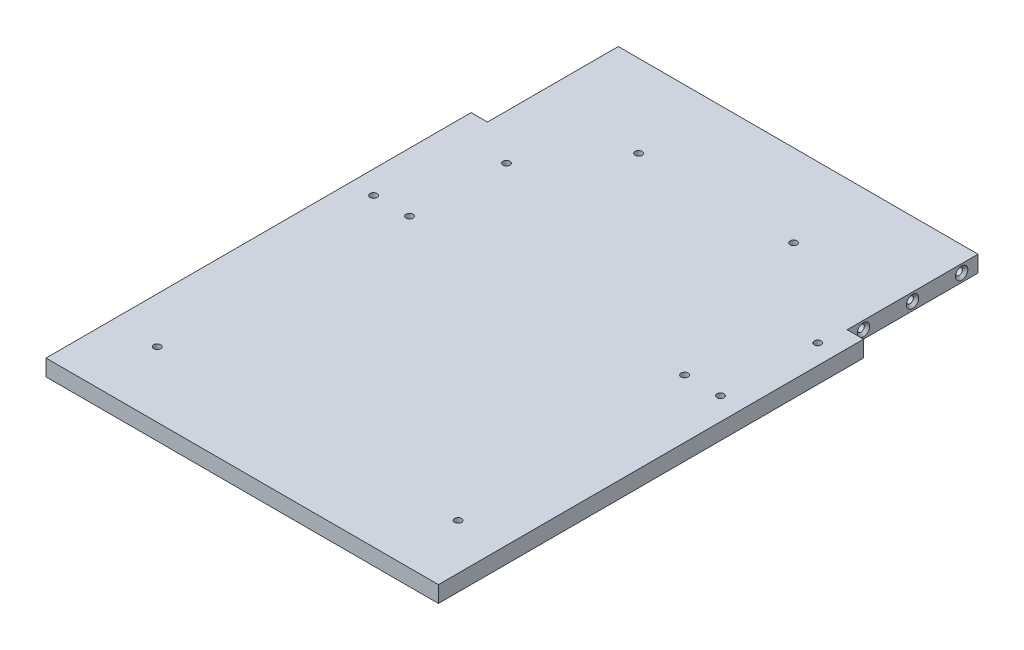
SolidWorks part; units mm, degrees
ref_plane "Front Plane" through (0, 0, 0) normal (0, 0, 1) x (1, 0, 0)
ref_plane "Top Plane" through (0, 0, 0) normal (0, 1, 0) x (1, 0, 0)
ref_plane "Right Plane" through (0, 0, 0) normal (1, 0, 0) x (0, 0, -1)
sketch "Sketch1" plane through (0, 0, 0) normal (0, 1, 0) x (1, 0, 0)
  line L0 (-6.35, 0) -> (-6.35, -50.8)
  line L1 (-6.35, 0) -> (-146.05, 0)
  line L2 (0, -50.8) -> (0, -215.9)
  line L3 (0, -215.9) -> (-152.4, -215.9)
  line L4 (-152.4, -50.8) -> (-152.4, -215.9)
  line L5 (-6.35, -50.8) -> (0, -50.8)
  line L6 (-146.05, 0) -> (-146.05, -50.8)
  line L7 (-146.05, -50.8) -> (-152.4, -50.8)
  point P7 (-3.175, -50.8)
  dimension "D1" = 152.4
  dimension "D2" = 215.9
  dimension "D3" = 50.8
  dimension "D4" = 6.35
  dimension "D5" = 6.35
  dimension "D6" = 50.8
extrude "Boss-Extrude1" add sketch "Sketch1" along normal blind 6.35
sketch "Sketch2" plane through (-6.35, 0, 0) normal (1, 0, 0) x (0, 0, -1)
  line L0 (-50.8, 6.35) -> (-50.8, 0) construction
  line L1 (-50.8, 6.35) -> (-50.8, 0) construction
  line L2 (-50.8, 0) -> (0, 0) construction
  circle A0 centre (-44.45, 3.175) radius 1.8288
  circle A1 centre (-25.4, 3.175) radius 1.8288
  circle A2 centre (-6.35, 3.175) radius 1.8288
  dimension "D4" = 3.175
  dimension "D5" = 3.175
  dimension "D6" = 3.6576
  dimension "D7" = 3.6576
  dimension "D8" = 3.6576
  dimension "D1" = 6.35
  dimension "D2" = 25.4
  dimension "D3" = 44.45
hole_wizard "#6-32 Tapped Hole1" positions "Sketch3" profile "Sketch4" tap size "#6-32" standard "ANSI Inch"
sketch "Sketch3" plane through (-6.35, 0, 0) normal (1, 0, 0) x (0, 0, -1)
  point P0 (-44.45, 3.175)
  point P3 (-25.4, 3.175)
  point P6 (-6.35, 3.175)
sketch "Sketch4" plane through (-6.35, 3.175, 44.45) normal (0, 1, 0) x (0, 0, -1)
  line L0 (0, 0) -> (0, 12.7)
  line L1 (0, 12.7) -> (1.3525, 11.8873)
  line L2 (1.3525, 11.8873) -> (1.3525, 1.0351)
  line L3 (1.3525, 1.0351) -> (2.3876, 0)
  line L5 (2.3876, 0) -> (0, 0)
  line L6 (-1.3525, 1.0351) -> (-2.3876, 0) construction
  line L10 (0, 12.7) -> (-1.3526, 11.8873) construction
  line L11 (0, -6.35) -> (0, 107.95) construction
  dimension "Tap Drill Dia." = 2.7051
  dimension "Tap Drill Depth" = 12.7
  dimension "Near C'Sink Dia." = 4.7752
  dimension "Near C'Sink Angle" = 90
  dimension "Drill Angle" = 118
cosmetic thread "Hole Thread1" parameters "D1"=10.16, "D2"=3.5052
cosmetic thread "Hole Thread2" parameters "D1"=10.16, "D2"=3.5052
cosmetic thread "Hole Thread3" parameters "D1"=10.16, "D2"=3.5052
sketch "Sketch5" plane through (-146.05, 0, 0) normal (-1, 0, 0) x (0, 0, 1)
  circle A0 centre (6.35, 3.175) radius 1.8288
  circle A1 centre (25.4, 3.175) radius 1.8288
  circle A2 centre (44.45, 3.175) radius 1.8288
  dimension "D1" = 3.6576
  dimension "D2" = 3.6576
  dimension "D3" = 3.6576
hole_wizard "#6-32 Tapped Hole2" positions "Sketch6" profile "Sketch7" tap size "#6-32" standard "ANSI Inch"
sketch "Sketch6" plane through (-146.05, 0, 0) normal (-1, 0, 0) x (0, 0, 1)
  point P0 (6.35, 3.175)
  point P3 (25.4, 3.175)
  point P6 (44.45, 3.175)
sketch "Sketch7" plane through (-146.05, 3.175, 6.35) normal (0, 1, 0) x (0, 0, 1)
  line L0 (0, 0) -> (0, 12.7)
  line L1 (0, 12.7) -> (1.3525, 11.8873)
  line L2 (1.3525, 11.8873) -> (1.3525, 1.0351)
  line L3 (1.3525, 1.0351) -> (2.3876, 0)
  line L5 (2.3876, 0) -> (0, 0)
  line L6 (-1.3525, 1.0351) -> (-2.3876, 0) construction
  line L10 (0, 12.7) -> (-1.3526, 11.8873) construction
  line L11 (0, -6.35) -> (0, 107.95) construction
  dimension "Tap Drill Dia." = 2.7051
  dimension "Tap Drill Depth" = 12.7
  dimension "Near C'Sink Dia." = 4.7752
  dimension "Near C'Sink Angle" = 90
  dimension "Drill Angle" = 118
cosmetic thread "Hole Thread4" parameters "D1"=10.16, "D2"=3.5052
cosmetic thread "Hole Thread5" parameters "D1"=10.16, "D2"=3.5052
cosmetic thread "Hole Thread6" parameters "D1"=10.16, "D2"=3.5052
sketch "Sketch9" plane through (0, 6.35, 0) normal (0, 1, 0) x (1, 0, 0)
  line L0 (-152.4, -215.9) -> (0, -215.9) construction
  line L1 (-152.4, -50.8) -> (-152.4, -215.9) construction
  line L2 (0, -215.9) -> (0, -50.8) construction
  circle A0 centre (-134.62, -190.5) radius 1.8288
  circle A1 centre (-17.78, -190.5) radius 1.8288
  dimension "D1" = 17.78
  dimension "D2" = 25.4
  dimension "D3" = 17.78
  dimension "D4" = 3.6576
  dimension "D5" = 3.6576
hole_wizard "#6-32 Tapped Hole3" positions "Sketch12" profile "Sketch13" tap size "#6-32" standard "ANSI Inch" end condition up to next
sketch "Sketch12" plane through (0, 6.35, 0) normal (0, 1, 0) x (1, 0, 0)
  point P0 (-134.62, -190.5)
  point P3 (-17.78, -190.5)
sketch "Sketch13" plane through (-134.62, 6.35, 190.5) normal (1, 0, 0) x (0, 0, 1)
  line L0 (0, 0) -> (0, 6.35)
  line L1 (0, 6.35) -> (1.3525, 6.35)
  line L2 (1.3525, 6.35) -> (1.3525, 0)
  line L5 (1.3525, 0) -> (0, 0)
  line L11 (0, -6.35) -> (0, 107.95) construction
  dimension "Thru Tap Drill Dia." = 2.7051
  dimension "Thru Tap Drill Depth" = 6.35
cosmetic thread "Hole Thread7" parameters "D2"=3.5052
cosmetic thread "Hole Thread8" parameters "D2"=3.5052
sketch "Sketch16" plane through (0, 6.35, 0) normal (0, 1, 0) x (1, 0, 0)
  line L0 (-6.35, -50.8) -> (-6.35, 0) construction
  line L1 (-6.35, 0) -> (-146.05, 0) construction
  circle A0 centre (-45.974, -32.004) radius 1.8288
  circle A1 centre (-106.172, -32.004) radius 1.8288
  dimension "D1" = 39.624
  dimension "D2" = 32.004
  dimension "D3" = 60.198
  dimension "D4" = 32.004
  dimension "D5" = 3.6576
  dimension "D6" = 3.6576
hole_wizard "#6-32 Tapped Hole5" positions "Sketch19" profile "Sketch18" tap size "#6-32" standard "ANSI Inch" end condition up to next
sketch "Sketch19" plane through (0, 6.35, 0) normal (0, 1, 0) x (1, 0, 0)
  point P0 (-106.172, -32.004)
  point P3 (-45.974, -32.004)
sketch "Sketch18" plane through (-106.172, 6.35, 32.004) normal (1, 0, 0) x (0, 0, 1)
  line L0 (0, 0) -> (0, 6.35)
  line L1 (0, 6.35) -> (1.3525, 6.35)
  line L2 (1.3525, 6.35) -> (1.3525, 0)
  line L5 (1.3525, 0) -> (0, 0)
  line L11 (0, -6.35) -> (0, 107.95) construction
  dimension "Thru Tap Drill Dia." = 2.7051
  dimension "Thru Tap Drill Depth" = 6.35
cosmetic thread "Hole Thread11" parameters "D2"=3.5052
cosmetic thread "Hole Thread12" parameters "D2"=3.5052
sketch "Sketch20" plane through (0, 6.35, 0) normal (0, 1, 0) x (1, 0, 0)
  line L0 (0, -50.8) -> (-6.35, -50.8) construction
  line L1 (0, -215.9) -> (0, -50.8) construction
  line L2 (-146.05, -50.8) -> (-152.4, -50.8) construction
  line L4 (-152.4, -50.8) -> (-152.4, -215.9) construction
  circle A0 centre (-128.524, -60.96) radius 1.8987
  circle A1 centre (-129.54, -97.5981) radius 1.8987
  circle A2 centre (-143.4846, -97.6122) radius 1.8987
  circle A3 centre (-7.62, -60.96) radius 1.8987
  circle A4 centre (-22.7076, -97.6122) radius 1.8986
  circle A5 centre (-8.763, -97.6122) radius 1.8987
  dimension "D1" = 10.16
  dimension "D2" = 7.62
  dimension "D3" = 36.6522
  dimension "D4" = 8.763
  dimension "D5" = 13.9446
  dimension "D6" = 36.6522
  dimension "D7" = 3.7973
  dimension "D8" = 3.7973
  dimension "D9" = 3.7973
  dimension "D10" = 3.7973
  dimension "D11" = 3.7973
  dimension "D12" = 3.7973
  dimension "D13" = 10.16
  dimension "D14" = 36.6522
  dimension "D15" = 13.9446
  dimension "D16" = 36.6522
  dimension "D17" = 23.876
  dimension "D18" = 22.86
hole_wizard "#6-32 Tapped Hole6" positions "Sketch21" profile "Sketch22" tap size "#6-32" standard "ANSI Inch" end condition through all
sketch "Sketch21" plane through (0, 6.35, 0) normal (0, 1, 0) x (1, 0, 0)
  point P0 (-128.524, -60.96)
  point P3 (-129.54, -97.5981)
  point P6 (-143.4846, -97.6122)
  point P9 (-7.62, -60.96)
  point P12 (-8.763, -97.6122)
  point P15 (-22.7076, -97.6122)
sketch "Sketch22" plane through (-128.524, 6.35, 60.96) normal (1, 0, 0) x (0, 0, 1)
  line L0 (0, 0) -> (0, 6.35)
  line L1 (0, 6.35) -> (1.3525, 6.35)
  line L2 (1.3525, 6.35) -> (1.3525, 0)
  line L5 (1.3525, 0) -> (0, 0)
  line L11 (0, -6.35) -> (0, 107.95) construction
  dimension "Thru Tap Drill Dia." = 2.7051
  dimension "Thru Tap Drill Depth" = 6.35
cosmetic thread "Hole Thread13" parameters "D2"=3.5052
cosmetic thread "Hole Thread14" parameters "D2"=3.5052
cosmetic thread "Hole Thread15" parameters "D2"=3.5052
cosmetic thread "Hole Thread16" parameters "D2"=3.5052
cosmetic thread "Hole Thread17" parameters "D2"=3.5052
cosmetic thread "Hole Thread18" parameters "D2"=3.5052
